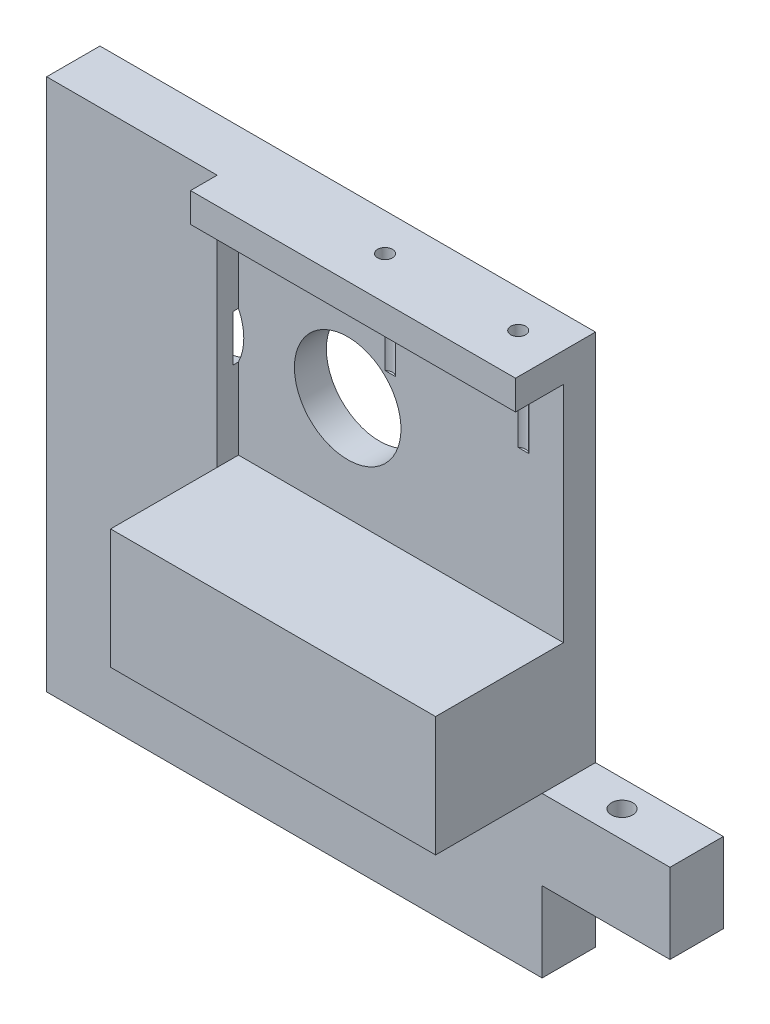
SolidWorks part; units mm, degrees
ref_plane "Front Plane" through (0, 0, 0) normal (0, 0, 1) x (1, 0, 0)
ref_plane "Top Plane" through (0, 0, 0) normal (0, 1, 0) x (1, 0, 0)
ref_plane "Right Plane" through (0, 0, 0) normal (1, 0, 0) x (0, 0, -1)
sketch "Sketch1" plane through (0, 0, 0) normal (0, 0, 1) x (1, 0, 0)
  line L1 (-76.1871, 64.9281) -> (16.8129, 64.9281)
  line L2 (-76.1871, 64.9281) -> (-76.1871, -35.0719)
  line L3 (-76.1871, -35.0719) -> (16.8129, -35.0719)
  line L4 (16.8129, 64.9281) -> (16.8129, -35.0719)
  dimension "D1" = 93
  dimension "D2" = 100
extrude "Boss-Extrude2" add sketch "Sketch1" along normal blind 10 contours L1 L4 L3 L2
sketch "Sketch3" plane through (0, 0, 0) normal (0, 0, -1) x (-1, 0, 0)
  line L0 (76.1871, -35.0719) -> (-16.8129, -35.0719) construction
  line L1 (-16.8129, 64.9281) -> (-6.8129, 64.9281)
  line L2 (-16.8129, 64.9281) -> (-16.8129, -35.0719)
  line L3 (-16.8129, -35.0719) -> (-6.8129, -35.0719)
  line L4 (-6.8129, 64.9281) -> (-6.8129, -35.0719)
  line L5 (-16.8129, 64.9281) -> (-16.8129, -35.0719) construction
  dimension "D1" = 0
  dimension "D2" = 0
  dimension "D3" = 10
  dimension "D4" = 100
extrude "Boss-Extrude3" add sketch "Sketch3" along normal blind 0.01
sketch "Sketch4" plane through (16.8129, 0, 0) normal (1, 0, 0) x (0, 0, -1)
  line L0 (-10, 64.9281) -> (-10, -35.0719) construction
  line L1 (-10, -5.0719) -> (0.01, -5.0719)
  line L2 (-10, -5.0719) -> (-10, -20.0719)
  line L3 (-10, -20.0719) -> (0.01, -20.0719)
  line L4 (0.01, -5.0719) -> (0.01, -20.0719)
  line L5 (0.01, 64.9281) -> (0.01, -35.0719) construction
  line L6 (-10, -35.0719) -> (0.01, -35.0719) construction
  dimension "D1" = 15
  dimension "D2" = 15
extrude "Boss-Extrude4" add sketch "Sketch4" along normal blind 24
sketch "Sketch5" plane through (0, -5.0719, 0) normal (0, 1, 0) x (1, 0, 0)
  line L0 (40.8129, -10) -> (16.8129, -10) construction
  line L2 (16.8129, 0.01) -> (16.8129, -10) construction
  circle A0 centre (26.8129, -5) radius 2
  dimension "D2" = 4
  dimension "D3" = 10
  dimension "D1" = 5
extrude "Cut-Extrude1" cut sketch "Sketch5" against normal blind 50
sketch "Sketch6" plane through (0, 0, -0.01) normal (0, 0, -1) x (-1, 0, 0)
  line L0 (-16.8129, -35.0719) -> (-6.8129, -35.0719) construction
  line L1 (-16.8129, -20.0719) -> (-16.8129, -35.0719) construction
  circle A0 centre (-1.8129, -24.5719) radius 7.5
  dimension "D1" = 15
  dimension "D2" = 10.5
  dimension "D3" = 15
sketch "Sketch7" plane through (0, 0, 0) normal (0, 0, -1) x (-1, 0, 0)
  line L0 (76.1871, -35.0719) -> (-6.8129, -35.0719) construction
  line L2 (-16.8129, 64.9281) -> (-16.8129, -5.0719) construction
  circle A0 centre (23.6871, 36.9281) radius 10
  dimension "D1" = 20
  dimension "D2" = 72
  dimension "D3" = 40.5
extrude "Cut-Extrude3" cut sketch "Sketch7" against normal blind 50
extrude "Extrude-Thin1" add sketch "Sketch7<2>" along normal blind 1 from surface thin starting at face at (-13.6871, 36.9281, 10) thin type one direction reverse wall 2
sketch "Sketch7<2>" plane through (0, 0, 0) normal (0, 0, -1) x (-1, 0, 0) same geometry as "Sketch7"
extrude "Extrude-Thin2" add sketch "Sketch6" along normal blind 1 from surface thin starting at face at (-0.4371, 1.1781, 10) thin type one direction reverse wall 2
sketch "Sketch8" plane through (0, 64.9281, 0) normal (0, 1, 0) x (1, 0, 0)
  line L0 (-76.1871, -10) -> (16.8129, -10) construction
  line L1 (16.8129, 0.01) -> (6.8129, 0.01)
  line L2 (16.8129, 0.01) -> (16.8129, -10)
  line L3 (16.8129, -10) -> (6.8129, -10)
  line L4 (6.8129, 0.01) -> (6.8129, -10)
  line L5 (16.8129, 0.01) -> (6.8129, -10) construction
  line L6 (16.8129, -10) -> (6.8129, 0.01) construction
  line L7 (6.8129, 0.01) -> (6.8129, 0) construction
  circle A0 centre (9.3129, -6.99) radius 1.4
  circle A1 centre (-15.6871, -6.99) radius 1.4
  point P4 (11.8129, -4.995)
  dimension "D1" = 25
  dimension "D3" = 2.8
  dimension "D5" = 7
  dimension "D6" = 7
extrude "Cut-Extrude4" cut sketch "Sketch8" against normal blind 20 contours A1 | A0 region at (-15.6871, 64.9281, 6.99)
sketch "Sketch14" plane through (0, 0, 10) normal (0, 0, 1) x (1, 0, 0)
  line L0 (16.8129, 64.9281) -> (16.8129, -5.0719) construction
  line L1 (-44.1871, 17.4281) -> (16.8129, 17.4281)
  line L2 (-44.1871, 17.4281) -> (-44.1871, 59.4281)
  line L3 (-44.1871, 59.4281) -> (16.8129, 59.4281)
  line L4 (16.8129, 17.4281) -> (16.8129, 59.4281)
  circle A0 centre (-23.6871, 36.9281) radius 8 construction
  dimension "D1" = 42
  dimension "D2" = 19.5
  dimension "D3" = 20.5
extrude "Cut-Extrude8" cut sketch "Sketch14" against normal blind 4
sketch "Sketch15" plane through (0, 0, 0) normal (0, 0, -1) x (-1, 0, 0)
  circle A0 centre (23.6871, 36.9281) radius 10
  circle A1 centre (23.6871, 36.9281) radius 10 construction
  dimension "D1" = 20
  dimension "D2" = 0
sketch "Sketch16" plane through (0, 0, 10) normal (0, 0, 1) x (1, 0, 0)
  line L1 (-44.1871, 59.4281) -> (16.8129, 59.4281)
  line L2 (-44.1871, 59.4281) -> (-44.1871, 64.9281)
  line L3 (-44.1871, 64.9281) -> (16.8129, 64.9281)
  line L4 (16.8129, 59.4281) -> (16.8129, 64.9281)
extrude "Boss-Extrude5" add sketch "Sketch16" along normal blind 5
sketch "Sketch17" plane through (0, 0, 10) normal (0, 0, 1) x (1, 0, 0)
  line L0 (16.8129, 17.4281) -> (16.8129, -5.0719) construction
  line L1 (-44.1871, 17.4281) -> (16.8129, 17.4281)
  line L2 (-44.1871, 17.4281) -> (-44.1871, -5.0719)
  line L3 (-44.1871, -5.0719) -> (16.8129, -5.0719)
  line L4 (16.8129, 17.4281) -> (16.8129, -5.0719)
extrude "Boss-Extrude6" add sketch "Sketch17" along normal blind 20
sketch "Sketch19" plane through (0, 0, 0) normal (0, 0, -1) x (-1, 0, 0)
  line L0 (-16.8129, 64.9281) -> (-16.8129, -5.0719) construction
  circle A0 centre (53.1871, 36.9281) radius 10
  circle A1 centre (23.6871, 36.9281) radius 10 construction
  dimension "D1" = 20
  dimension "D3" = 0
  dimension "D2" = 70
extrude "Cut-Extrude11" cut sketch "Sketch19" against normal blind 7
